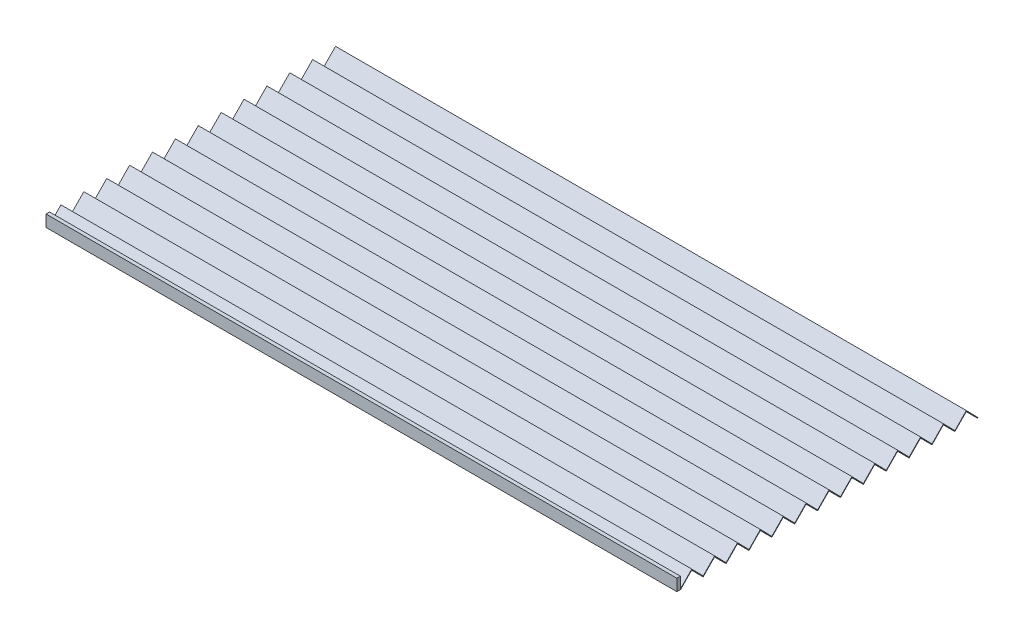
SolidWorks part; units mm, degrees
ref_plane "Front Plane" through (0, 0, 0) normal (0, 0, 1) x (1, 0, 0)
ref_plane "Top Plane" through (0, 0, 0) normal (0, 1, 0) x (1, 0, 0)
ref_plane "Right Plane" through (0, 0, 0) normal (1, 0, 0) x (0, 0, -1)
sketch "Sketch2" plane through (0, 0, 0) normal (0, 0, 1) x (1, 0, 0)
  line L1 (-270, 10) -> (270, 10)
  line L2 (-270, 10) -> (-270, 0)
  line L3 (-270, 0) -> (270, 0)
  line L4 (270, 10) -> (270, 0)
  point P4 (0, 0)
  dimension "D1" = 10
  dimension "D2" = 540
extrude "Boss-Extrude1" add sketch "Sketch2" along normal blind 3
sketch "Sketch3" plane through (270, 0, 0) normal (1, 0, 0) x (0, 0, -1)
  line L0 (0, 10) -> (254.6355, 10) construction
  line L1 (0, 0) -> (254.6355, 0) construction
  line L3 (0, 0) -> (9.7937, 10)
  line L4 (9.7937, 10) -> (19.5873, 0)
  line L5 (19.5873, 0) -> (29.381, 10)
  line L6 (29.381, 10) -> (39.1747, 0)
  line L7 (39.1747, 0) -> (48.9684, 10)
  line L8 (48.9684, 10) -> (58.762, 0)
  line L9 (58.762, 0) -> (68.5557, 10)
  line L10 (68.5557, 10) -> (78.3494, 0)
  line L11 (78.3494, 0) -> (88.1431, 10)
  line L12 (88.1431, 10) -> (97.9367, 0)
  line L13 (97.9367, 0) -> (107.7304, 10)
  line L14 (107.7304, 10) -> (117.5241, 0)
  line L15 (117.5241, 0) -> (127.3177, 10)
  line L16 (127.3177, 10) -> (137.1114, 0)
  line L17 (137.1114, 0) -> (146.9051, 10)
  line L18 (146.9051, 10) -> (156.6988, 0)
  line L20 (156.6988, 0) -> (166.4924, 10)
  line L21 (166.4924, 10) -> (176.2861, 0)
  line L22 (176.2861, 0) -> (186.0798, 10)
  line L23 (186.0798, 10) -> (195.8735, 0)
  line L24 (195.8735, 0) -> (205.6671, 10)
  line L25 (205.6671, 10) -> (215.4608, 0)
  line L26 (215.4608, 0) -> (225.2545, 10)
  line L27 (225.2545, 10) -> (235.0481, 0)
  line L28 (235.0481, 0) -> (244.8418, 10)
  line L29 (244.8418, 10) -> (254.6355, 0)
  line L30 (254.6355, 10) -> (254.6355, 0) construction
  line L32 (254.6355, 10) -> (254.6355, 0) construction
extrude "Extrude-Thin1" add sketch "Sketch3" against normal through all thin thin type mid plane wall 0.5
